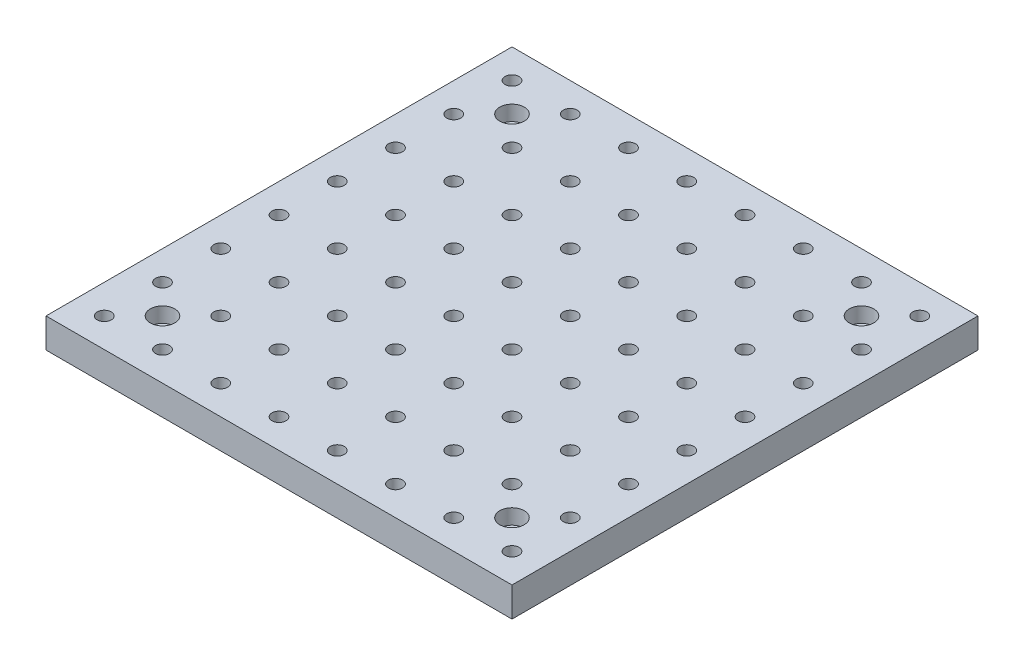
SolidWorks part; units mm, degrees
ref_plane "Front Plane" through (0, 0, 0) normal (0, 0, 1) x (1, 0, 0)
ref_plane "Top Plane" through (0, 0, 0) normal (0, 1, 0) x (1, 0, 0)
ref_plane "Right Plane" through (0, 0, 0) normal (1, 0, 0) x (0, 0, -1)
sketch "Sketch1" plane through (0, 0, 0) normal (0, 1, 0) x (1, 0, 0)
  line L0 (-87.5, 87.5) -> (-62.5, 87.5) construction
  line L1 (100, 100) -> (-100, 100)
  line L2 (100, 100) -> (100, -100)
  line L3 (100, -100) -> (-100, -100)
  line L4 (-100, 100) -> (-100, -100)
  line L5 (100, 100) -> (-100, -100) construction
  line L6 (100, -100) -> (-100, 100) construction
  line L7 (-87.5, 87.5) -> (-87.5, 62.5) construction
  circle A0 centre (-87.5, 87.5) radius 3
  circle A1 centre (-62.5, 87.5) radius 3
  circle A2 centre (-37.5, 87.5) radius 3
  circle A3 centre (-12.5, 87.5) radius 3
  circle A4 centre (12.5, 87.5) radius 3
  circle A5 centre (37.5, 87.5) radius 3
  circle A6 centre (62.5, 87.5) radius 3
  circle A7 centre (87.5, 87.5) radius 3
  circle A8 centre (-62.5, 62.5) radius 3
  circle A9 centre (-37.5, 62.5) radius 3
  circle A10 centre (-12.5, 62.5) radius 3
  circle A11 centre (12.5, 62.5) radius 3
  circle A12 centre (37.5, 62.5) radius 3
  circle A13 centre (62.5, 62.5) radius 3
  circle A14 centre (87.5, 62.5) radius 3
  circle A15 centre (-62.5, 37.5) radius 3
  circle A16 centre (-37.5, 37.5) radius 3
  circle A17 centre (-12.5, 37.5) radius 3
  circle A18 centre (12.5, 37.5) radius 3
  circle A19 centre (37.5, 37.5) radius 3
  circle A20 centre (62.5, 37.5) radius 3
  circle A21 centre (87.5, 37.5) radius 3
  circle A22 centre (-62.5, 12.5) radius 3
  circle A23 centre (-37.5, 12.5) radius 3
  circle A24 centre (-12.5, 12.5) radius 3
  circle A25 centre (12.5, 12.5) radius 3
  circle A26 centre (37.5, 12.5) radius 3
  circle A27 centre (62.5, 12.5) radius 3
  circle A28 centre (87.5, 12.5) radius 3
  circle A29 centre (-62.5, -12.5) radius 3
  circle A30 centre (-37.5, -12.5) radius 3
  circle A31 centre (-12.5, -12.5) radius 3
  circle A32 centre (12.5, -12.5) radius 3
  circle A33 centre (37.5, -12.5) radius 3
  circle A34 centre (62.5, -12.5) radius 3
  circle A35 centre (87.5, -12.5) radius 3
  circle A36 centre (-62.5, -37.5) radius 3
  circle A37 centre (-37.5, -37.5) radius 3
  circle A38 centre (-12.5, -37.5) radius 3
  circle A39 centre (12.5, -37.5) radius 3
  circle A40 centre (37.5, -37.5) radius 3
  circle A41 centre (62.5, -37.5) radius 3
  circle A42 centre (87.5, -37.5) radius 3
  circle A43 centre (-62.5, -62.5) radius 3
  circle A44 centre (-37.5, -62.5) radius 3
  circle A45 centre (-12.5, -62.5) radius 3
  circle A46 centre (12.5, -62.5) radius 3
  circle A47 centre (37.5, -62.5) radius 3
  circle A48 centre (62.5, -62.5) radius 3
  circle A49 centre (87.5, -62.5) radius 3
  circle A50 centre (-62.5, -87.5) radius 3
  circle A51 centre (-37.5, -87.5) radius 3
  circle A52 centre (-12.5, -87.5) radius 3
  circle A53 centre (12.5, -87.5) radius 3
  circle A54 centre (37.5, -87.5) radius 3
  circle A55 centre (62.5, -87.5) radius 3
  circle A56 centre (87.5, -87.5) radius 3
  circle A57 centre (-87.5, 62.5) radius 3
  circle A58 centre (-87.5, 37.5) radius 3
  circle A59 centre (-87.5, 12.5) radius 3
  circle A60 centre (-87.5, -12.5) radius 3
  circle A61 centre (-87.5, -37.5) radius 3
  circle A62 centre (-87.5, -62.5) radius 3
  circle A63 centre (-87.5, -87.5) radius 3
  point P0 (0, 0)
  point P8 (-87.5186, 62.5)
  point P9 (0, 0)
  dimension "D3" = 6
  dimension "D1" = 200
  dimension "D2" = 12.5
  dimension "D6" = 25
  dimension "D7" = 25
  dimension "D4" = 8
  dimension "D5" = 8
extrude "Boss-Extrude1" add sketch "Sketch1" against normal blind 12.7
sketch "Sketch2" plane through (0, 0, 0) normal (0, 1, 0) x (1, 0, 0)
  line L0 (-100, 100) -> (-100, -100) construction
  line L1 (-100, -100) -> (100, -100) construction
  line L2 (-75, -75) -> (75, -75) construction
  circle A0 centre (-75, -75) radius 5.25
  circle A1 centre (75, -75) radius 5.25
  circle A2 centre (75, 75) radius 5.25
  circle A3 centre (-75, 75) radius 5.25
  point P6 (0, 0)
  point P7 (0, 0)
  dimension "D1" = 10.5
  dimension "D2" = 25
  dimension "D3" = 25
  dimension "D6" = 150
  dimension "D7" = 150
  dimension "D4" = 2
  dimension "D5" = 2
extrude "Cut-Extrude1" cut sketch "Sketch2" against normal blind 6.5
sketch "Sketch3" plane through (0, -6.5, 0) normal (0, 1, 0) x (1, 0, 0)
  circle A0 centre (-75, -75) radius 1.65
  circle A1 centre (-75, -75) radius 5.25 construction
  point P2 (-74.9024, -75.8199)
  point P5 (0, 0)
  dimension "D1" = 3.3
extrude "Cut-Extrude2" cut sketch "Sketch3" against normal through all both and the other way through all
mirror "Mirror1" about plane through (0, 0, 0) normal (1, 0, 0) of "Cut-Extrude2" second plane through (0, 0, 0) second plane normal (0, 0, 1)
